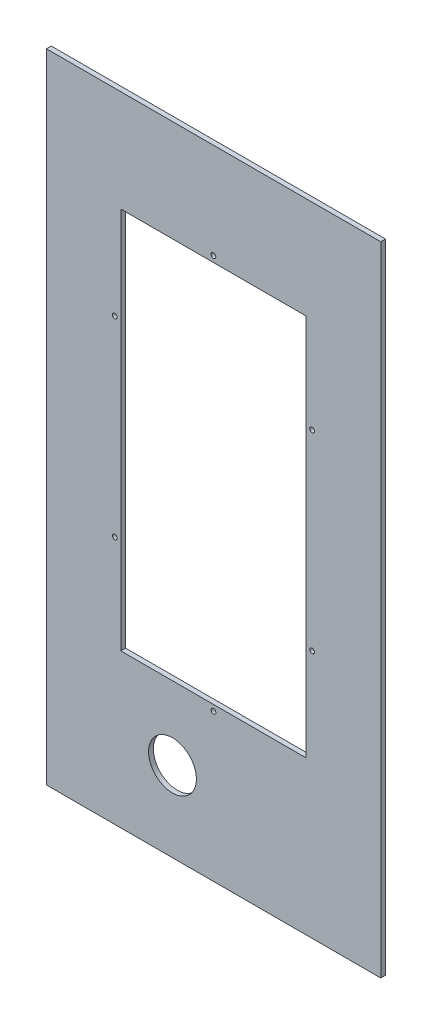
SolidWorks part; units mm, degrees
ref_plane "Спереди" through (0, 0, 0) normal (0, 0, 1) x (1, 0, 0)
ref_plane "Сверху" through (0, 0, 0) normal (0, 1, 0) x (1, 0, 0)
ref_plane "Справа" through (0, 0, 0) normal (1, 0, 0) x (0, 0, -1)
sketch "Эскиз1" plane through (0, 0, 0) normal (0, 1, 0) x (1, 0, 0)
  line L1 (-144.7882, -2.3414) -> (134.7883, -2.3414)
  line L2 (-144.7882, -2.3414) -> (-144.7882, -6.3414)
  line L3 (-144.7882, -6.3414) -> (134.7883, -6.3414)
  line L4 (134.7883, -2.3414) -> (134.7883, -6.3414)
extrude "Вытянуть1" add sketch "Эскиз1" along normal up to surface (533.2137 mm away)
sketch "Эскиз2" plane through (0, 0, 2.3414) normal (0, 0, -1) x (-1, 0, 0)
  circle A0 centre (39.3967, 66.9121) radius 20
extrude "Вырез-Вытянуть1" cut sketch "Эскиз2" against normal through all
sketch "Эскиз3" plane through (0, 0, 6.3414) normal (0, 0, 1) x (1, 0, 0)
  line L1 (-82.6488, 448.2137) -> (72.3512, 448.2137)
  line L2 (-82.6488, 448.2137) -> (-82.6488, 128.2137)
  line L3 (-82.6488, 128.2137) -> (72.3512, 128.2137)
  line L4 (72.3512, 448.2137) -> (72.3512, 128.2137)
extrude "Cut-Extrude1" cut sketch "Эскиз3" against normal through all
sketch "Sketch1" plane through (0, 0, 6.3414) normal (0, 0, 1) x (1, 0, 0)
  line L0 (72.3512, 448.2137) -> (-82.6488, 448.2137) construction
  line L1 (-82.6488, 448.2137) -> (-82.6488, 128.2137) construction
  line L2 (-5.1488, 447.7153) -> (-5.1488, 464.7544) construction
  line L3 (72.3512, 288.2137) -> (113.04, 288.2137) construction
  circle A0 centre (-87.6488, 368.2137) radius 2
  circle A1 centre (-87.6488, 208.2137) radius 2
  circle A2 centre (77.3512, 208.2137) radius 2
  circle A3 centre (77.3512, 368.2137) radius 2
  circle A4 centre (-5.1488, 453.2137) radius 2
  circle A5 centre (-5.1488, 123.2137) radius 2
  dimension "D1" = 80
  dimension "D3" = 5
  dimension "D2" = 5
extrude "Cut-Extrude2" cut sketch "Sketch1" against normal through all
